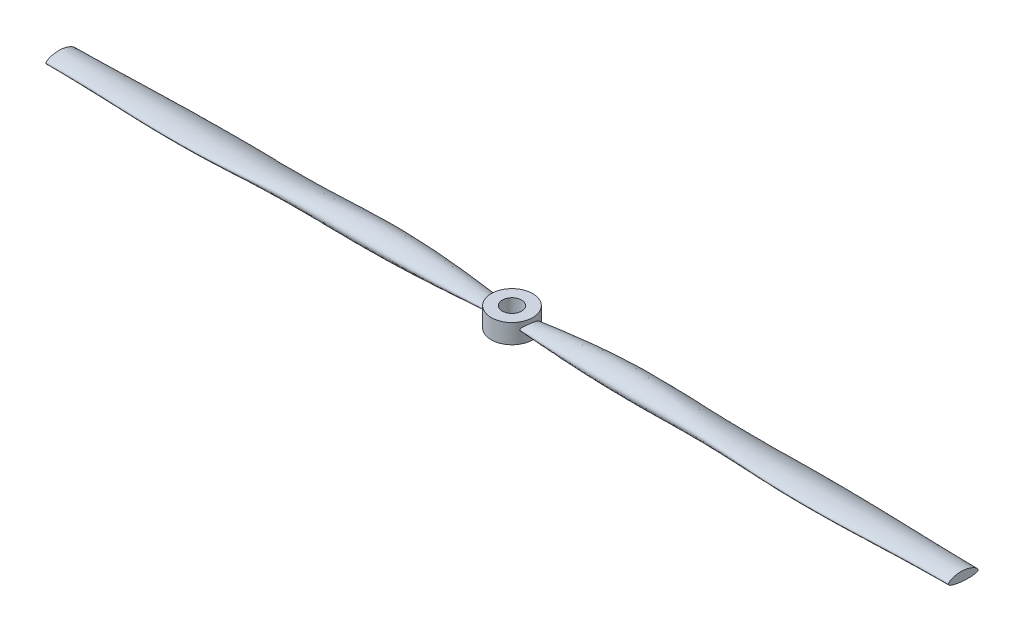
SolidWorks part; units mm, degrees
ref_plane "Front Plane" through (0, 0, 0) normal (0, 0, 1) x (1, 0, 0)
ref_plane "Top Plane" through (0, 0, 0) normal (0, 1, 0) x (1, 0, 0)
ref_plane "Right Plane" through (0, 0, 0) normal (1, 0, 0) x (0, 0, -1)
sketch "Sketch1" plane through (0, 0, 0) normal (0, 1, 0) x (1, 0, 0)
  circle A0 centre (0, 0) radius 7
  circle A1 centre (0, 0) radius 3.25
  dimension "D1" = 14
  dimension "D2" = 6.5
extrude "Boss-Extrude1" add sketch "Sketch1" along normal mid plane 6.5 contours A1 | A0 A1 region at (-6.802, 0, 0) region at (0, 0, 0)
sketch "Sketch2" plane through (0, 0, 0) normal (1, 0, 0) x (0, 0, -1)
  line L0 (-2.8978, 0.7765) -> (2.8978, -0.7765) construction
  line L1 (0, 0) -> (0, 1) construction
  spline S0 degree 3 poles (5.7343, -2.2535) (-5.796, 0.7549) (0.3216, 1.5264) (5.7343, -2.2535) (-5.796, 0.7549) (0.3216, 1.5264) knots -1 -0.763811 -0.487593 0 0.236189 0.512407 1 1.236189 1.512407 2 only from (-2.8978, 0.7765) to (-2.8978, 0.7765)
  point P4 (0, 0)
  dimension "D1" = 1
  dimension "D2" = 6
  dimension "D3" = 105
ref_plane "Plane1" through (46, 0, 0) normal (1, 0, 0) x (0, 0, -1)
ref_plane "Plane2" through (89, 0, 0) normal (1, 0, 0) x (0, 0, -1)
ref_plane "Plane3" through (152, 0, 0) normal (1, 0, 0) x (0, 0, -1)
sketch "Sketch3" plane through (46, 0, 0) normal (1, 0, 0) x (0, 0, -1)
  line L0 (-6.5707, 3.064) -> (6.5707, -3.064) construction
  line L1 (0, 0) -> (0, 5) construction
  spline S0 degree 3 poles (13.0886, -8.9481) (-13.0642, 2.2205) (2.0359, 7.4327) (13.0886, -8.9481) (-13.0642, 2.2205) (2.0359, 7.4327) knots -1 -0.784265 -0.456663 0 0.215735 0.543337 1 1.215735 1.543337 2 only from (-6.5707, 3.064) to (-6.5707, 3.064)
  point P5 (0, 0)
  dimension "D1" = 5
  dimension "D2" = 14.5
  dimension "D3" = 115
sketch "Sketch4" plane through (89, 0, 0) normal (1, 0, 0) x (0, 0, -1)
  line L0 (-7.5175, 2.7362) -> (7.5175, -2.7362) construction
  line L2 (0, 0) -> (0, 3.25) construction
  spline S0 degree 3 poles (14.8621, -7.6284) (-15.0714, 2.8596) (1.3074, 4.8096) (14.8621, -7.6284) (-15.0714, 2.8596) (1.3074, 4.8096) knots -1 -0.772662 -0.48273 0 0.227338 0.51727 1 1.227338 1.51727 2 only from (-7.5175, 2.7362) to (-7.5175, 2.7362)
  point P3 (0, 0)
  dimension "D1" = 3.25
  dimension "D2" = 16
  dimension "D3" = 110
sketch "Sketch5" plane through (152, 0, 0) normal (1, 0, 0) x (0, 0, -1)
  line L0 (-4.981, 0.4358) -> (4.981, -0.4358) construction
  line L2 (0, 0) -> (0, 2) construction
  line L3 (0, 0) -> (0, 1) construction
  spline S0 degree 3 poles (9.8413, -2.2954) (-9.8716, -0.6318) (0.2129, 3.196) (9.8413, -2.2954) (-9.8716, -0.6318) (0.2129, 3.196) knots -1 -0.748582 -0.481569 0 0.251418 0.518431 1 1.251418 1.518431 2 only from (-4.981, 0.4358) to (-4.981, 0.4358)
  point P4 (0, 0)
  dimension "D1" = 2
  dimension "D2" = 10
  dimension "D3" = 95
loft "Loft1" add profiles "Sketch2", "Sketch3", "Sketch4", "Sketch5" connector at (0, -0.3458, -2.7066) connector at (46, 3.0342, -3.6948) connector at (89, 3.5555, 1.2884) connector at (152, 1.7993, -1.3468)
mirror "Mirror1" about plane through (0, 0, 0) normal (1, 0, 0) of "Loft1"
extrude "Cut-Extrude1" cut sketch "Sketch1<3>" along normal up to surface and the other way up to surface contours A1 region at (0, 0, 0) up to face at (0, 3.25, 7) other way up to face at (0, -3.25, 7)
sketch "Sketch1<3>" plane through (0, 0, 0) normal (0, 1, 0) x (1, 0, 0) same geometry as "Sketch1"
